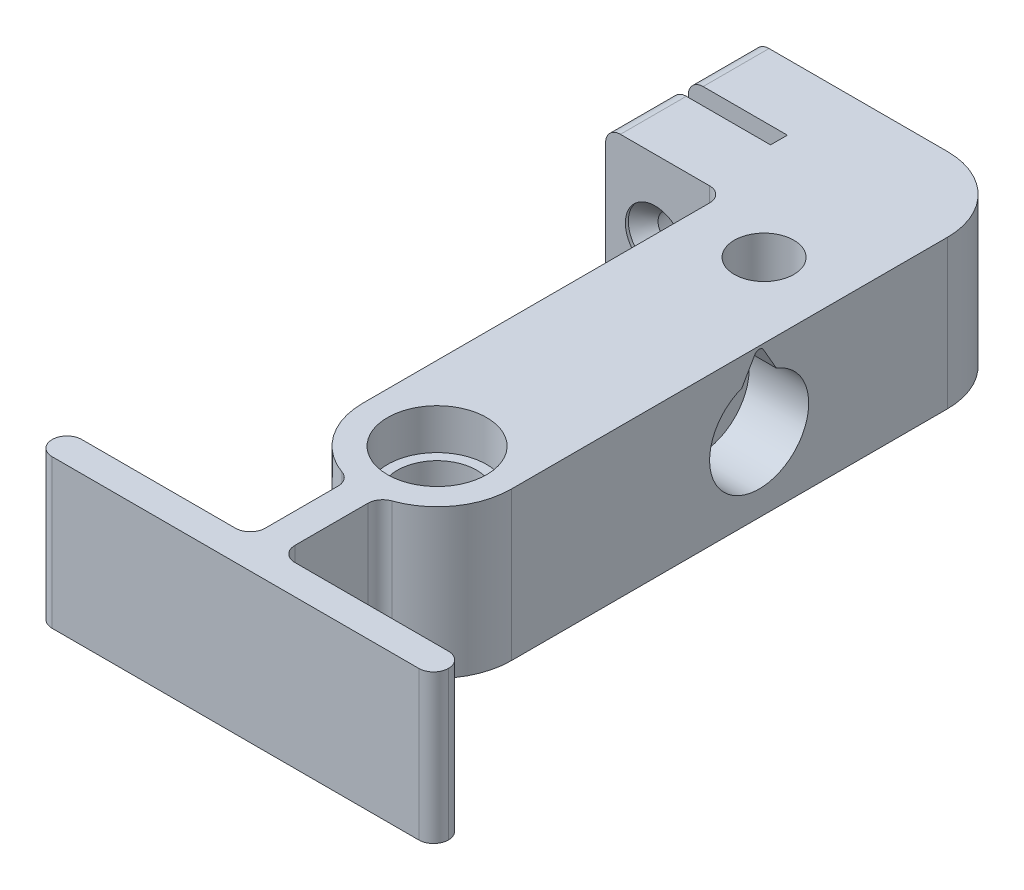
SolidWorks part; units mm, degrees
ref_plane "Front Plane" through (0, 0, 0) normal (0, 0, 1) x (1, 0, 0)
ref_plane "Top Plane" through (0, 0, 0) normal (0, 1, 0) x (1, 0, 0)
ref_plane "Right Plane" through (0, 0, 0) normal (1, 0, 0) x (0, 0, -1)
sketch "Sketch1" plane through (0, 0, 0) normal (0, 1, 0) x (1, 0, 0)
  line L0 (0, 22) -> (0, -22) construction
  line L1 (-7.5, 22) -> (7.5, 22)
  line L2 (-7.5, 22) -> (-7.5, -22)
  line L3 (-7.5, -22) -> (7.5, -22)
  line L4 (7.5, 22) -> (7.5, -22)
  line L5 (-7.5, 22) -> (7.5, -22) construction
  line L6 (-7.5, -22) -> (7.5, 22) construction
  circle A0 centre (0, -14.5) radius 4
  circle A1 centre (0, -14.5) radius 7.5
  point P0 (0, 0)
  dimension "D1" = 8
  dimension "D2" = 15
  dimension "D4" = 44
extrude "Boss-Extrude1" add sketch "Sketch1" along normal mid plane 15 contours L2 | L4 | A1 L4 L1 L2 | A1 A0 | L3 region at (0, 0, -6.6495) region at (0, 0, 7.2121)
sketch "Sketch2" plane through (0, 7.5, 0) normal (0, 1, 0) x (1, 0, 0)
  circle A0 centre (0, -14.5) radius 5
  dimension "D1" = 10
extrude "Cut-Extrude1" cut sketch "Sketch2" against normal blind 4.1
mirror "Mirror1" about plane through (0, 0, 0) normal (0, 1, 0) of "Cut-Extrude1"
sketch "Sketch12" plane through (0, -3.4, 0) normal (0, -1, 0) x (1, 0, 0)
  circle A0 centre (0, 14.5) radius 4 construction
  circle A1 centre (0, 14.5) radius 5
  circle A2 centre (0, 14.5) radius 5
  circle A3 centre (0, 14.5) radius 4
  dimension "D1" = 0
extrude "Cut-Extrude10" cut sketch "Sketch12" against normal blind 1
sketch "Sketch4" plane through (7.5, 0, 0) normal (1, 0, 0) x (0, 0, -1)
  line L0 (-3.1918, 0) -> (3.917, 0) construction
  line L1 (8.75, 4.6837) -> (12.25, 4.6837) construction
  line L2 (-9.5, 7.5) -> (-19.5, 7.5) construction
  line L3 (-9.5, 7.5) -> (-19.5, 7.5)
  line L4 (-14.5, 7.5) -> (-14.5, -7.5) construction
  line L5 (22, -7.5) -> (-14.5, -7.5) construction
  line L6 (10.5, 0) -> (10.5, 7.5) construction
  line L9 (22, 7.5) -> (-14.5, 7.5) construction
  line L10 (10.5, 7.7148) -> (8.75, 4.6837)
  line L11 (10.5, 7.7148) -> (12.25, 4.6837)
  circle A1 centre (10.5, 0) radius 5
  circle A3 centre (10.5, 6.7148) radius 0.5
  dimension "D1" = 25
  dimension "D2" = 10
  dimension "D5" = 1
  dimension "D4" = 3.5
extrude "Cut-Extrude3" cut sketch "Sketch4" against normal blind 6 contours A1 | A1 L11 L10 | A3 region at (7.5, 5.5753, -10.5) region at (7.5, 6.7148, -10.5) region at (7.5, 0, -10.5)
mirror "Mirror2" about plane through (0, 0, 0) normal (1, 0, 0) of "Cut-Extrude3"
sketch "Sketch18" plane through (0, -7.5, 0) normal (0, -1, 0) x (1, 0, 0)
  line L0 (0, -41.3409) -> (0, 22.3101) construction
  line L4 (7.5, -3.75) -> (-7.5, -3.75) construction
  line L5 (-19.5, -22) -> (-7.5, -22)
  line L6 (7.5, -29.5) -> (7.5, -22)
  line L7 (7.5, -22) -> (7.5, 14.5) construction
  line L8 (-7.5, -22) -> (7.5, -22)
  line L9 (-7.5, -22) -> (-7.5, 14.5) construction
  line L10 (0, -22) -> (0, -37) construction
  line L11 (0, -37) -> (-19.5, -37)
  line L13 (-19.5, -22) -> (-19.5, -37)
  circle A1 centre (0, -29.5) radius 7.5
  line M10 (-7.5, -22) -> (7.5, -22)
  dimension "D1" = 12
extrude "Boss-Extrude3" add sketch "Sketch18" against normal up to surface (15 mm away) contours A1 L6 L8 | A1 M10 | A1 | A1 L13 L11 region at (-12.5923, -7.5, -29.5) region at (5.8247, -7.5, -23.6753) region at (0, -7.5, -29.5) up to face at (0, 7.5, 19.5)
sketch "Sketch7" plane through (0, 7.5, 0) normal (0, 1, 0) x (1, 0, 0)
  line L0 (-19.5, 29.5) -> (7.5, 29.5) construction
  line L8 (7.5, 29.5) -> (7.5, -14.5) construction
  line L9 (-19.5, 28.65) -> (-9.5, 28.65)
  line L10 (-19.5, 28.65) -> (-19.5, 30.35)
  line L11 (-9.5, 28.65) -> (-9.5, 30.35)
  line L12 (-19.5, 30.35) -> (-9.5, 30.35)
  line L13 (-19.5, 28.65) -> (-9.5, 30.35) construction
  line L14 (-9.5, 28.65) -> (-19.5, 30.35) construction
  line L15 (-19.5, 22) -> (-19.5, 37) construction
  point P8 (-14.5, 29.5)
  dimension "D1" = 10
  dimension "D2" = 1.7
extrude "Cut-Extrude7" cut sketch "Sketch7" against normal up to next
sketch "Sketch8" plane through (-40.2452, 0, -37) normal (0, 0, 1) x (1, 0, 0)
  line L5 (20.7452, 0) -> (40.2452, 0) construction
  line L8 (20.7452, 7.5) -> (20.7452, -7.5) construction
  line L9 (40.2452, 7.5) -> (40.2452, -7.5) construction
  circle A2 centre (25.7452, 0) radius 1.5
  dimension "D2" = 5
  dimension "D3" = 3
extrude "Cut-Extrude8" cut sketch "Sketch8" along normal up to surface (15 mm away) contours A2
hole_wizard "CSK for M3 Flat Head Machine Screw1" positions "Sketch9" profile "Sketch10" countersink size "M3" standard "ANSI Metric"
sketch "Sketch9" plane through (-83.1458, 0, -22) normal (0, 0, 1) x (1, 0, 0)
  point P6 (68.6458, 0)
  point P17 (0, 0)
  point P18 (0, 0)
  point P19 (0, 0)
  point P20 (0, 0)
sketch "Sketch10" plane through (-14.5, 0, -22) normal (1, 0, 0) x (0, -1, 0)
  line L0 (0, 0) -> (0, 5.9013)
  line L1 (0, 5.9013) -> (1.5, 5)
  line L2 (1.5, 5) -> (1.5, 1.8)
  line L3 (1.5, 1.8) -> (3, 0.3)
  line L4 (3, 0.3) -> (3, 0)
  line L6 (3, 0) -> (0, 0)
  line L7 (-1.5, 1.8) -> (-3, 0.3) construction
  line L10 (0, 5.9013) -> (-1.5, 5) construction
  line L11 (0, -6.35) -> (0, 107.95) construction
  dimension "Hole Dia." = 3
  dimension "Hole Depth" = 5
  dimension "C'Sink Dia." = 6
  dimension "C'Sink Angle" = 90
  dimension "Drill Angle" = 118
  dimension "Head Clearance" = 0.3
sketch "Sketch11" plane through (15, 0, -37) normal (0, 0, 1) x (1, 0, 0)
  line L7 (-34.5, 7.5) -> (-34.5, -7.5) construction
  line L8 (-29.5, -3.4641) -> (-26.5, -1.7321)
  line L15 (-26.5, -1.7321) -> (-26.5, 1.7321)
  line L16 (-26.5, 1.7321) -> (-29.5, 3.4641)
  line L17 (-29.5, 3.4641) -> (-32.5, 1.7321)
  line L18 (-32.5, 1.7321) -> (-32.5, -1.7321)
  line L19 (-32.5, -1.7321) -> (-29.5, -3.4641)
  circle A0 centre (-29.5, 0) radius 3 construction
  dimension "D1" = 6
extrude "Cut-Extrude9" cut sketch "Sketch11" along normal blind 3
sketch "Sketch13" plane through (-44.6536, 0, -30.35) normal (0, 0, 1) x (1, 0, 0)
  line L0 (35.1536, -7.5) -> (35.1536, 7.5) construction
  line L2 (35.1536, -7.5) -> (35.1536, 7.5)
  line L3 (35.1536, 0) -> (44.6536, 0) construction
  line L4 (44.6536, 7.5) -> (44.6536, -7.5) construction
  line L5 (35.1536, 7.5) -> (42.6536, 0)
  line L6 (35.1536, -7.5) -> (42.6536, 0)
  dimension "D1" = 45
extrude "Cut-Extrude11" cut sketch "Sketch13" along normal up to surface (1.7 mm away) contours L5 L6 L2 up to face at (-13, 0, -28.65)
sketch "Sketch16" plane through (0, -7.5, 0) normal (0, -1, 0) x (1, 0, 0)
  line L0 (0, 42.718) -> (0, -5.4521) construction
  line L2 (-1.5, 31.8485) -> (1.5, 31.8485)
  line L3 (-1.5, 31.8485) -> (-1.5, 21.8485)
  line L4 (-1.5, 21.8485) -> (1.5, 21.8485)
  line L5 (1.5, 31.8485) -> (1.5, 21.8485)
  line L6 (-1.5, 31.8485) -> (1.5, 21.8485) construction
  line L7 (-1.5, 21.8485) -> (1.5, 31.8485) construction
  line L8 (-20, 34.8485) -> (20, 34.8485)
  line L9 (-20, 34.8485) -> (-20, 31.8485)
  line L10 (-20, 31.8485) -> (20, 31.8485)
  line L11 (20, 34.8485) -> (20, 31.8485)
  line L12 (-20, 34.8485) -> (20, 31.8485) construction
  line L13 (-20, 31.8485) -> (20, 34.8485) construction
  arc A0 (7.5, 14.5) -> (-7.5, 14.5) centre (0, 14.5) ccw construction
  point P1 (0, 26.8485)
  point P11 (0, 33.3485)
  arc M14 (7.5, 14.5) -> (-7.5, 14.5) centre (0, 14.5) ccw
  dimension "D1" = 3
  dimension "D2" = 10
  dimension "D3" = 40
extrude "Boss-Extrude2" add sketch "Sketch16" against normal up to surface (15 mm away) contours L5 L2 L3 M14 | L11 L8 L9 L10 L2 region at (0, -7.5, 33.3485) region at (0, -7.5, 26.899) up to face at (-8.677, 7.5, -20.9594)
fillet "Fillet8" radius 1.5 13 edges at (20, 0, 31.8485) (20, 0, 34.8485) (-20, 0, 34.8485) (-20, 0, 31.8485) (-1.5, 0, 31.8485) (-1.5, 0, 21.8485) (1.5, 0, 21.8485) (1.5, 0, 31.8485) (-19.5, -7.5, -25.325) (-19.5, -7.5, -33.675) (-19.5, 7.5, -33.675) (-19.5, 7.5, -25.325) (-7.5, 0, -22)
sketch "Sketch19" plane through (0, -7.5, 0) normal (0, -1, 0) x (1, 0, 0)
  line L0 (0, 4.3088) -> (0, -5.4508) construction
  circle A0 centre (0, -18.5) radius 3
  circle A2 centre (0, 14.5) radius 5 construction
  dimension "D1" = 6
  dimension "D2" = 33
extrude "Cut-Extrude12" cut sketch "Sketch19" against normal up to next contours A0
